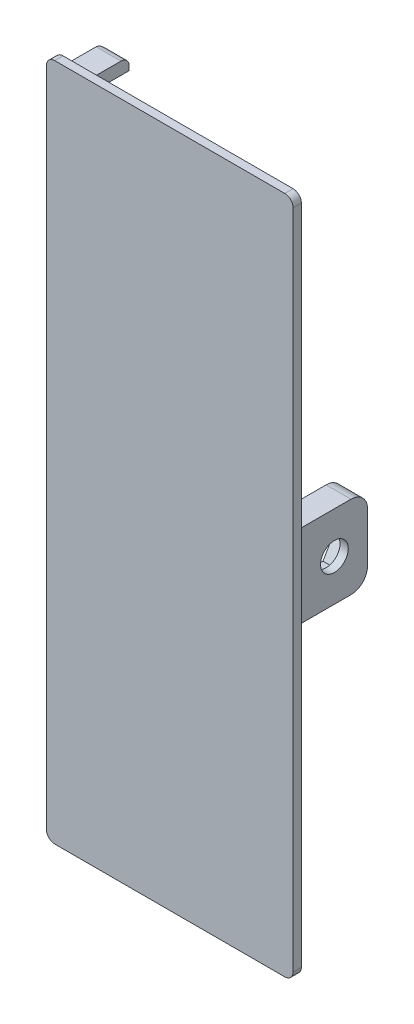
SolidWorks part; units mm, degrees
ref_plane "Front Plane" through (0, 0, 0) normal (0, 0, 1) x (1, 0, 0)
ref_plane "Top Plane" through (0, 0, 0) normal (0, 1, 0) x (1, 0, 0)
ref_plane "Right Plane" through (0, 0, 0) normal (1, 0, 0) x (0, 0, -1)
sketch "Sketch1" plane through (0, 0, 0) normal (0, 0, 1) x (1, 0, 0)
  line L1 (14.9, -41) -> (-14.9, -41)
  line L2 (14.9, -41) -> (14.9, 41)
  line L3 (14.9, 41) -> (-14.9, 41)
  line L4 (-14.9, -41) -> (-14.9, 41)
  line L5 (14.9, -41) -> (-14.9, 41) construction
  line L6 (14.9, 41) -> (-14.9, -41) construction
  point P0 (0, 0)
  dimension "D1" = 82
  dimension "D2" = 29.8
extrude "Boss-Extrude1" add sketch "Sketch1" along normal blind 1
sketch "Sketch2" plane through (0, 0, 0) normal (0, 0, -1) x (-1, 0, 0)
  line L0 (-14.9, -41) -> (-14.9, 41) construction
  line L1 (13.9, -39.95) -> (-13.9, -39.95)
  line L2 (13.9, -39.95) -> (13.9, 39.95)
  line L3 (13.9, 39.95) -> (-13.9, 39.95)
  line L4 (-13.9, -39.95) -> (-13.9, 39.95)
  line L5 (13.9, -39.95) -> (-13.9, 39.95) construction
  line L6 (13.9, 39.95) -> (-13.9, -39.95) construction
  point P0 (0, 0)
  dimension "D1" = 79.9
  dimension "D2" = 1
extrude "Boss-Extrude2" add sketch "Sketch2" along normal blind 0.001
sketch "Sketch3" plane through (0, 0, 0) normal (0, 0, -1) x (-1, 0, 0)
  line L0 (-13.9, -39.95) -> (-13.9, 39.95) construction
  line L1 (-13.9, 5) -> (-10.9, 5)
  line L2 (-13.9, 5) -> (-13.9, -5)
  line L3 (-13.9, -5) -> (-10.9, -5)
  line L4 (-10.9, 5) -> (-10.9, -5)
  dimension "D1" = 3
  dimension "D2" = 10
  dimension "D3" = 5
extrude "Boss-Extrude3" add sketch "Sketch3" along normal blind 9
sketch "Sketch4" plane through (10.9, 0, 0) normal (-1, 0, 0) x (0, 0, 1)
  line L0 (-9, 5) -> (-0.001, 5) construction
  line L1 (-3.3834, 2.8) -> (-6.6166, 2.8)
  line L2 (-6.6166, 2.8) -> (-8.2332, 0)
  line L3 (-8.2332, 0) -> (-6.6166, -2.8)
  line L4 (-6.6166, -2.8) -> (-3.3834, -2.8)
  line L5 (-3.3834, -2.8) -> (-1.7668, 0)
  line L6 (-1.7668, 0) -> (-3.3834, 2.8)
  line L8 (1, 41) -> (1, -41) construction
  circle A0 centre (-5, 0) radius 2.8 construction
  dimension "D1" = 5.6
  dimension "D2" = 6
extrude "Cut-Extrude1" cut sketch "Sketch4" against normal blind 2
sketch "Sketch5" plane through (12.9, 0, 0) normal (-1, 0, 0) x (0, 0, 1)
  line L1 (-9, 5) -> (-0.001, 5) construction
  line L2 (0, -5) -> (0, 5) construction
  circle A0 centre (-5, 0) radius 1.675
  dimension "D1" = 5
  dimension "D2" = 5
  dimension "D3" = 3.35
extrude "Cut-Extrude2" cut sketch "Sketch5" against normal up to surface (1 mm away) up to face at (13.9, 0, -2.2505)
chamfer "Chamfer1" distance 1.5 angle 45 1 edges at (10.9, 0, -0.001)
sketch "Sketch7" plane through (0, 0, 0) normal (0, 0, -1) x (-1, 0, 0)
  line L1 (13.9, 39.95) -> (12.4, 39.95)
  line L2 (13.9, 39.95) -> (13.9, 36.95)
  line L3 (13.9, 36.95) -> (12.4, 36.95)
  line L4 (12.4, 39.95) -> (12.4, 36.95)
  line L5 (13.9, 39.95) -> (10.9, 39.95)
  line L6 (13.9, 39.95) -> (13.9, 38.45)
  line L7 (13.9, 38.45) -> (10.9, 38.45)
  line L8 (10.9, 39.95) -> (10.9, 38.45)
  line L9 (13.9, -39.95) -> (12.4, -39.95)
  line L10 (13.9, -39.95) -> (13.9, -36.95)
  line L11 (13.9, -36.95) -> (12.4, -36.95)
  line L12 (12.4, -39.95) -> (12.4, -36.95)
  line L13 (13.9, -39.95) -> (10.9, -39.95)
  line L14 (13.9, -39.95) -> (13.9, -38.45)
  line L15 (13.9, -38.45) -> (10.9, -38.45)
  line L16 (10.9, -39.95) -> (10.9, -38.45)
  line M9 (13.9, -39.95) -> (-13.9, -39.95)
  line M11 (-13.9, 39.95) -> (13.9, 39.95)
  line M12 (13.9, 39.95) -> (13.9, -39.95)
  dimension "D1" = 3
  dimension "D2" = 1.5
extrude "Boss-Extrude4" add sketch "Sketch7" along normal blind 5 contours L8 L7 L4 M11 | L7 L4 M12 M11 | L2 L7 L4 L3 | L15 L11 L12 M12 | L10 L15 L12 M9 | L16 L12 L15 M9 region at (-13.15, 39.2, 0) region at (-13.15, -37.7, 0) region at (-11.65, 39.2, 0) region at (-13.15, 37.7, 0) region at (-13.15, -39.2, 0) region at (-11.65, -39.2, 0)
fillet "Fillet1" radius 1 4 edges at (-14.9, 41, 0.5) (14.9, 41, 0.5) (14.9, -41, 0.5) (-14.9, -41, 0.5)
fillet "Fillet2" radius 2 2 edges at (12.4, 5, -9) (12.4, -5, -9)
fillet "Fillet3" radius 1 4 edges at (-12.4, -39.95, -5) (-13.9, -38.45, -5) (-13.9, 38.45, -5) (-12.4, 39.95, -5)
